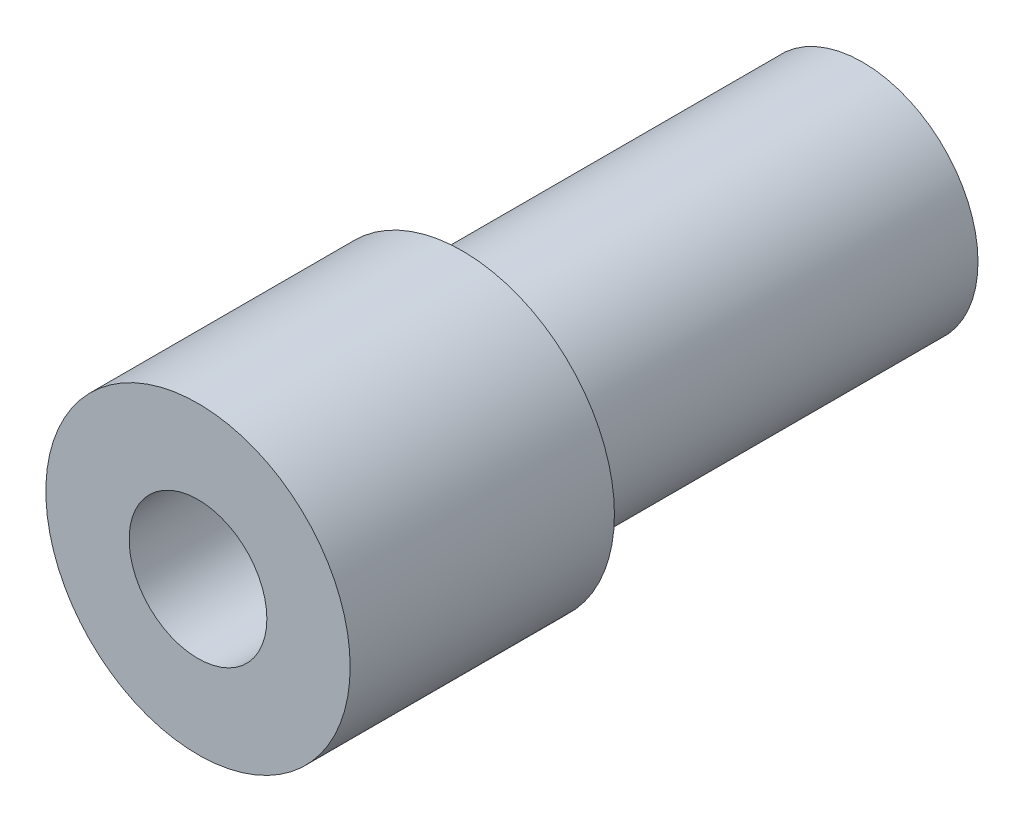
SolidWorks part; units mm, degrees
ref_plane "Спереди" through (0, 0, 0) normal (0, 0, 1) x (1, 0, 0)
ref_plane "Сверху" through (0, 0, 0) normal (0, 1, 0) x (1, 0, 0)
ref_plane "Справа" through (0, 0, 0) normal (1, 0, 0) x (0, 0, -1)
sketch "Эскиз1" plane through (0, 0, 0) normal (0, 0, 1) x (1, 0, 0)
  circle A0 centre (0, 0) radius 14.4
  circle A1 centre (0, 0) radius 8.6
  circle A2 centre (0, 0) radius 16
  circle A3 centre (0, 0) radius 19
  dimension "D1" = 28.8
  dimension "D2" = 17.2
  dimension "D3" = 1.6
  dimension "D4" = 3
extrude "Бобышка-Вытянуть1" add sketch "Эскиз1" against normal blind 80 contours A0 A1 region at (-13.9927, 0, 0)
extrude "Бобышка-Вытянуть2" add sketch "Эскиз1<3>" along normal blind 3 contours A3 A2 | A2 A0 | A0 A1 region at (-13.9927, 0, 0) region at (-15.5475, 0, 0) region at (-18.4626, 0, 0)
sketch "Эскиз1<3>" plane through (0, 0, 0) normal (0, 0, 1) x (1, 0, 0) same geometry as "Эскиз1"
extrude "Бобышка-Вытянуть3" add sketch "Эскиз1<5>" against normal blind 30 contours A3 A2 region at (-18.4626, 0, 0)
sketch "Эскиз1<5>" plane through (0, 0, 0) normal (0, 0, 1) x (1, 0, 0) same geometry as "Эскиз1"
extrude "Бобышка-Вытянуть4" add sketch "Эскиз1<6>" along normal blind 3 from surface contours A1 region at (0, 0, 0) starting at face at (8.6, 0, -80)
sketch "Эскиз1<6>" plane through (0, 0, 0) normal (0, 0, 1) x (1, 0, 0) same geometry as "Эскиз1"
equation "\"DTailTube\"= 16mm'Диаметр трубки хвостового оперения"
equation "\"FusLenght\"= 700mm"
equation "\"DMotor\"= 35.2mm"
equation "\"MotorArm\"= 320mm"
equation "\"DFus\"= 150mm"
equation "\"DFusTube\"= 30mm'Диаметр трубки внутри фюзеляжа"
equation "\"FusTubeHeight\"= 40mm"
equation "\"FusCentralPartLenght\"= 410mm"
equation "\"FusNoseLenght\"= 150mm"
equation "\"WingOffset\"= 1mm'Расстояние от внутренней поверхности фюзеляжа до профиля крыла по вертикали"
equation "\"EllipseRatio\"= 0.95'Центральная часть фюзеляжа - эллипс. Этот параметр - отношение длин осей эллипса"
equation "\"FrameOffset\"= 0.6mm"
equation "\"DThreadedInsert\"= 3mm'Внешний диамер резьбовых втулок"
equation "\"CenterSectionLenght\"= 140mm'Длина центроплана"
equation "\"b\"= 1700mm'Размах"
equation "\"cwr\"= 236mm'Корневая хорда крыла"
equation "\"TR\"= 0.75'Сужение крыла"
equation "\"cwt\"= \"TR\" * \"cwr\"'Концевая хорда крыла"
equation "\"DWingMainSpar\"= 16mm'Диаметр главного лонжерона крыла"
equation "\"DWingSecondSpar\"= 8mm'Диаметр второго лонжерона крыла"
equation "\"WingSparsDistance\"= 80mm'Расстояния между отверстиями по лонжерон крыла"
equation "\"c\"= 210mm'САХ крыла"
equation "\"FusTubeLenght\"= \"FusLenght\"-90mm'Длина трубки фюзеляжа"
equation "\"bt\"=291mm'Высота лопатки хвоста"
equation "\"ct\"=182mm'Корневая хорда хвоста"
equation "\"lambda_t\"=0.3'Доля хвоста, занатая рулем высоты"
equation "\"TailTubeLenght\"=680mm'Длина хвостовой балки"
equation "\"DStringer\"=6mm'Диаметр стрингеров"
equation "\"TailConnectorBaseLenght\"=20mm'Высота основания конектора хвоста"
equation "\"CargoHolderHoleDistance\"=30mm'Расстояние между крепежными отверстиями для держателя груза"
equation "\"FuselageThickness\"=1.2mm'Толщина фюзеляжа"
equation "\"DTailSpar\"=6mm'Диаметр лонжерона хвостового оперения"
equation "\"TailSparDistance\"=40mm'Расстояние между лонжеронами хвостового оперения"
equation "\"CrossSectionWidth\"=15mm'Ширина кольцевой части шпангоута"
equation "\"D1@Эскиз1\"=\"DFusTube\"-1.2"
equation "\"D2@Эскиз1\"=\"DTailTube\"+1.2"
